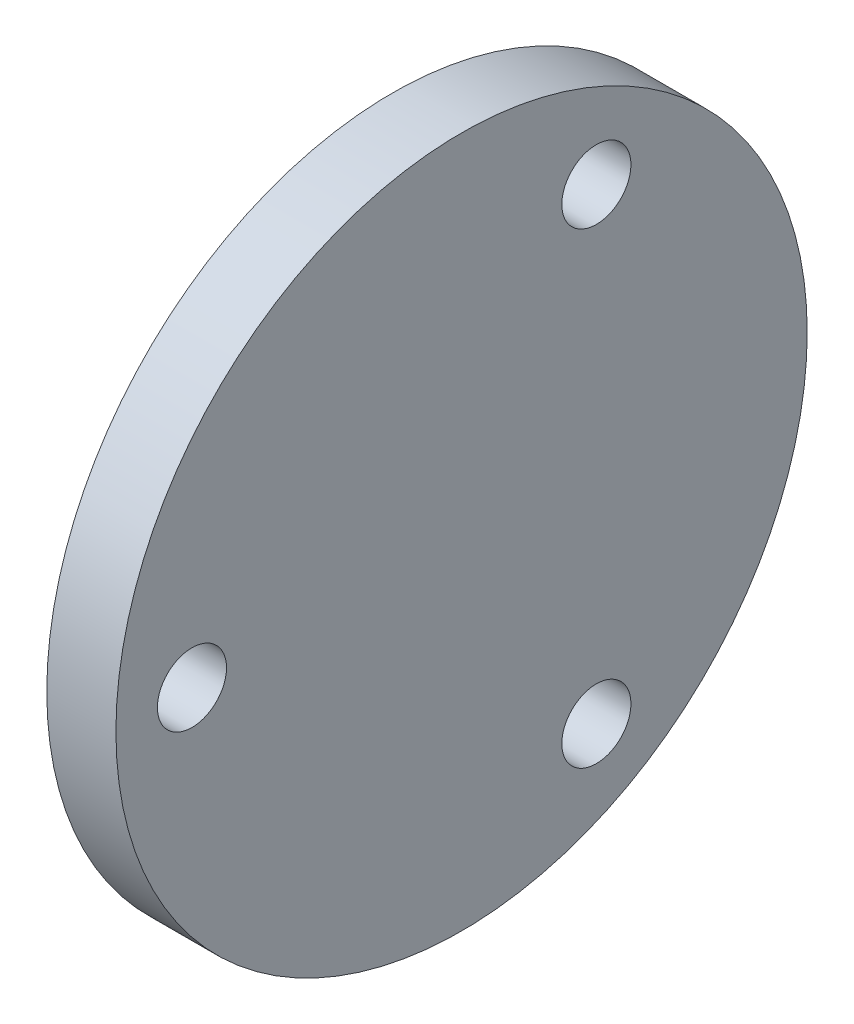
SolidWorks part; units mm, degrees
ref_plane "Front Plane" through (0, 0, 0) normal (1, 0, 0) x (0, 1, 0)
ref_plane "Top Plane" through (0, 0, 0) normal (0, 0, 1) x (0, 1, 0)
ref_plane "Right Plane" through (0, 0, 0) normal (0, 1, 0) x (-1, 0, 0)
sketch "Sketch1" plane through (0, 0, 0) normal (1, 0, 0) x (0, 1, 0)
  line L0 (0, 0) -> (0, 19.5) construction
  line L1 (0, 19.5) -> (16.8875, -9.75) construction
  line L2 (16.8875, -9.75) -> (-16.8875, -9.75) construction
  line L3 (-16.8875, -9.75) -> (0, 19.5) construction
  circle A0 centre (0, 0) radius 25
  circle A1 centre (0, 0) radius 19.5 construction
  circle A2 centre (0, 19.5) radius 2.5
  circle A3 centre (16.8875, -9.75) radius 2.5
  circle A4 centre (-16.8875, -9.75) radius 2.5
  dimension "D1" = 50
  dimension "D2" = 39
  dimension "D3" = 5
  dimension "D4" = 5
  dimension "D6" = 5
  dimension "D5" = 30
extrude "Boss-Extrude1" add sketch "Sketch1" along normal blind 5
